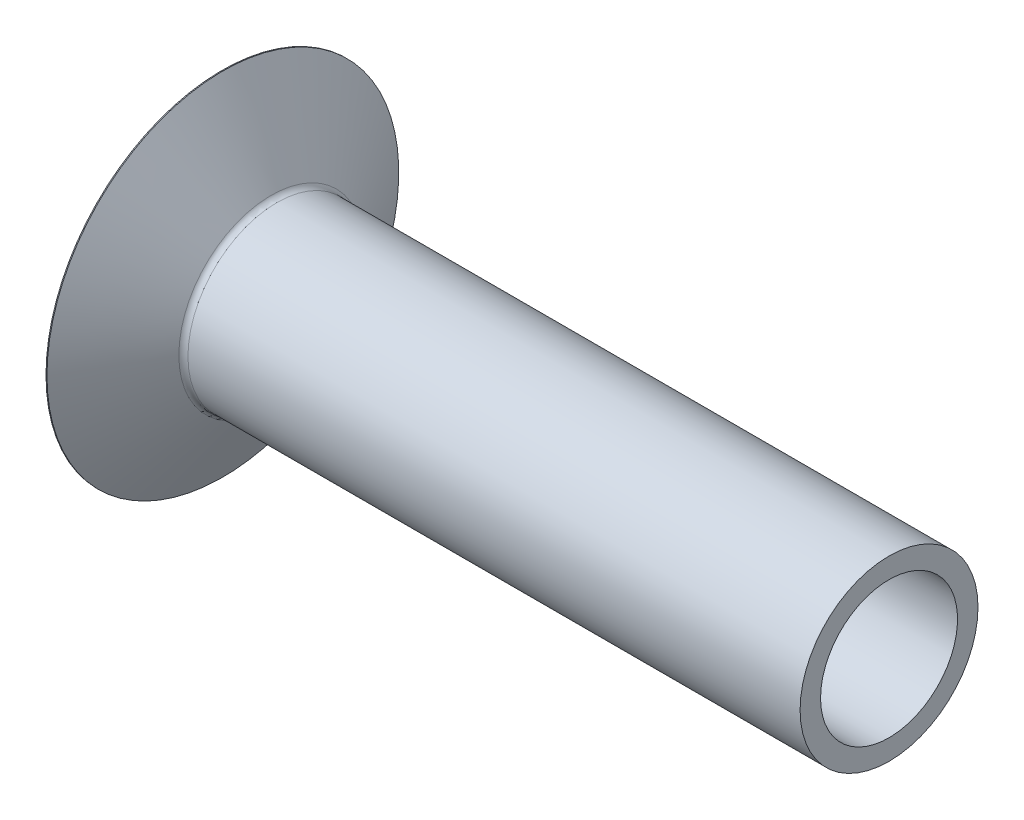
SolidWorks part; units mm, degrees
ref_plane "Front" through (0, 0, 0) normal (0, 0, 1) x (1, 0, 0)
ref_plane "Top" through (0, 0, 0) normal (0, 1, 0) x (1, 0, 0)
ref_plane "Right" through (0, 0, 0) normal (1, 0, 0) x (0, 0, -1)
sketch "Sketch1" plane through (0, 0, 0) normal (0, 0, 1) x (1, 0, 0)
  line L0 (-55.4117, 0) -> (10.9263, 0) construction
  line L1 (30, 0) -> (30, 4)
  line L2 (30, 4) -> (2.4732, 4)
  line L3 (2.2134, 4.15) -> (0.0426, 7.91)
  line L4 (0.0426, 7.91) -> (0, 7.91)
  line L5 (0, 7.91) -> (0, 0)
  line L6 (30, 0) -> (0, 0)
  line L7 (2.4732, 4) -> (2.3, 4) construction
  line L8 (2.2134, 4.15) -> (2.3, 4) construction
  arc A0 (2.4732, 4) -> (2.2134, 4.15) centre (2.4732, 4.3) cw
  dimension "r" = 0.3
  dimension "d" = 8
  dimension "l" = 30
  dimension "D3" = 60
  dimension "dk" = 15.82
  dimension "k" = 2.3
revolve "Base-Revolve" add sketch "Sketch1" angle 360 about L0
sketch "Sketch3" plane through (0, 0, 0) normal (0, 0, 1) x (1, 0, 0)
  line L0 (-6.108, 0) -> (1.7598, 0) construction
  line L2 (30, 3.08) -> (21.65, 3.08)
  line L4 (21.65, 3.08) -> (19.8718, 0)
  line L5 (30, 0) -> (30, 3.08)
  line L6 (19.8718, 0) -> (30, 0)
  line L7 (30, -4) -> (30, 4) construction
  dimension "D1" = 60
  dimension "dt" = 6.16
  dimension "t" = 8.35
revolve "Cut-Revolve1" cut sketch "Sketch3" angle 360 about L0
